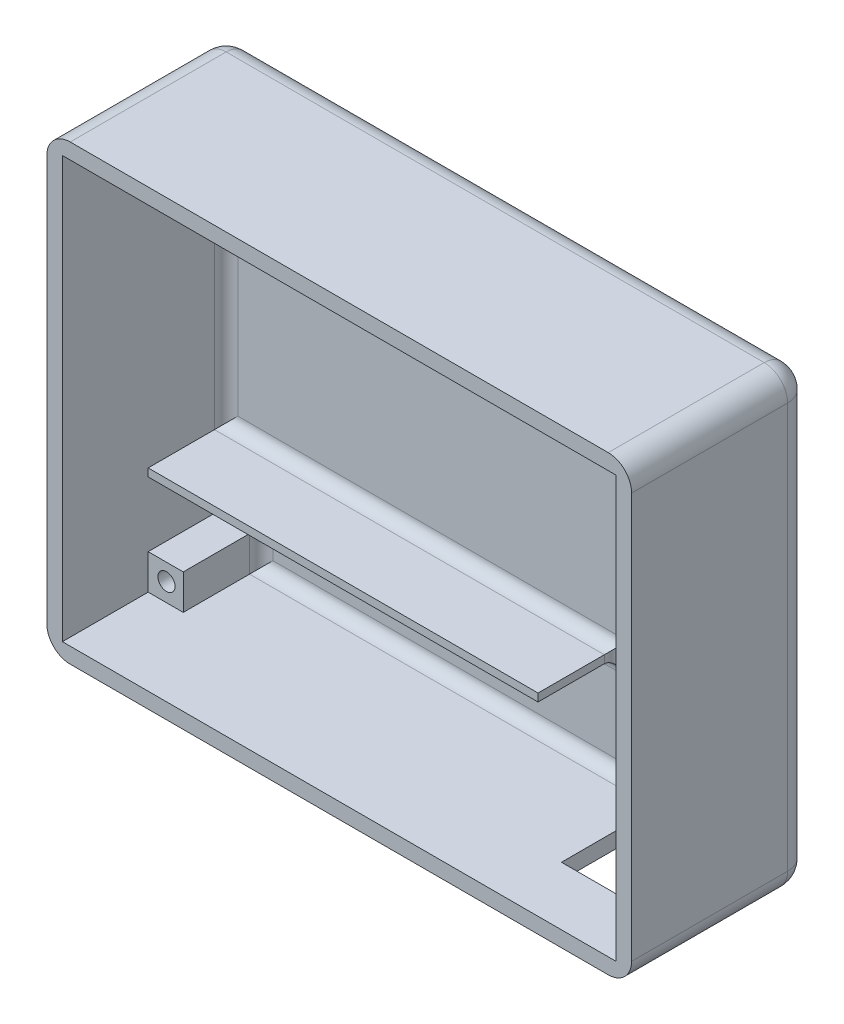
SolidWorks part; units mm, degrees
ref_plane "Front Plane" through (0, 0, 0) normal (0, 0, 1) x (1, 0, 0)
ref_plane "Top Plane" through (0, 0, 0) normal (0, 1, 0) x (1, 0, 0)
ref_plane "Right Plane" through (0, 0, 0) normal (1, 0, 0) x (0, 0, -1)
sketch "Sketch2" plane through (0, 0, 0) normal (0, 0, 1) x (1, 0, 0)
  line L1 (0, 0) -> (75, 0)
  line L2 (0, 0) -> (0, 58)
  line L3 (0, 58) -> (75, 58)
  line L4 (75, 0) -> (75, 58)
  dimension "D1" = 75
  dimension "D2" = 58
extrude "Body creation" add sketch "Sketch2" along normal blind 23
shell "Thikness of walls" thickness 2 removed face at (37.5, 29, 23)
ref_plane "Plane1" through (0, 29, 0) normal (0, -1, 0) x (-1, 0, 0)
sketch "Sketch6" plane through (0, 0, 2) normal (0, 0, 1) x (1, 0, 0)
  line L1 (2, 56) -> (6.5, 56)
  line L2 (2, 56) -> (2, 51.5)
  line L3 (2, 51.5) -> (6.5, 51.5)
  line L4 (6.5, 56) -> (6.5, 51.5)
  line L5 (73, 56) -> (68.5, 56)
  line L6 (73, 56) -> (73, 51.5)
  line L7 (73, 51.5) -> (68.5, 51.5)
  line L8 (68.5, 56) -> (68.5, 51.5)
  dimension "D1" = 4.5
extrude "Corner rect." add sketch "Sketch6" along normal blind 10
sketch "Sketch8" plane through (0, 0, 23) normal (0, 0, 1) x (1, 0, 0)
  line L0 (4.35, 53.65) -> (4.35, 51.5) construction
  line L1 (2, 51.5) -> (6.5, 51.5) construction
  line L2 (6.5, 53.65) -> (4.35, 53.65) construction
  line L3 (6.5, 51.5) -> (6.5, 56) construction
  line L4 (68.5, 53.65) -> (70.65, 53.65) construction
  line L7 (70.65, 53.65) -> (70.65, 51.5) construction
  line L9 (68.5, 56) -> (68.5, 51.5) construction
  line L10 (68.5, 51.5) -> (73, 51.5) construction
  circle A0 centre (4.35, 53.65) radius 1.1
  circle A1 centre (70.65, 53.65) radius 1.1
  dimension "D1" = 2.2
  dimension "D2" = 2.15
  dimension "D3" = 2.15
extrude "Screw hole" cut sketch "Sketch8" against normal up to surface (23 mm away) up to face at (37.5, 29, 0)
sketch "Sketch10" plane through (0, 0, 0) normal (0, 0, -1) x (-1, 0, 0)
  circle A0 centre (-70.65, 53.65) radius 1.85
  circle A1 centre (-4.35, 53.65) radius 1.85
  dimension "D1" = 3.7
extrude "Screw head" cut sketch "Sketch10" against normal blind 4
mirror "Mirror to other side" about plane through (0, 29, 0) normal (0, -1, 0) of "Screw head", "Corner rect.", "Screw hole"
sketch "Sketch5" plane through (0, 0, 0) normal (0, -1, 0) x (1, 0, 0)
  line L0 (0, 0) -> (75, 0) construction
  line L1 (67.5, 15.5) -> (58.5, 15.5)
  line L2 (67.5, 15.5) -> (67.5, 4.5)
  line L3 (67.5, 4.5) -> (58.5, 4.5)
  line L4 (58.5, 15.5) -> (58.5, 4.5)
  line L7 (63, 15.5) -> (63, 4.5) construction
  line L8 (75, 23) -> (75, 0) construction
  dimension "D1" = 11
  dimension "D2" = 9
  dimension "D3" = 15.5
  dimension "D4" = 12
extrude "Ports cut out" cut sketch "Sketch5" against normal up to surface (2 mm away) up to face at (37.5, 2, 12.25)
sketch "Sketch11" plane through (0, 0, 2) normal (0, 0, 1) x (1, 0, 0)
  line L0 (2, 51.5) -> (2, 6.5) construction
  line L1 (6.5, 51.5) -> (52, 51.5)
  line L3 (2, 15.8) -> (52, 15.8)
  line L5 (6.5, 52.5) -> (52, 52.5)
  line L6 (2, 14.8) -> (52, 14.8)
  line L7 (52, 15.8) -> (52, 14.8)
  line L8 (52, 52.5) -> (52, 51.5)
  line L9 (6.5, 52.5) -> (6.5, 51.5)
  line L10 (2, 15.8) -> (2, 14.8)
  line L11 (2, 56) -> (2, 2) construction
  line L12 (68.5, 56) -> (67.25, 56)
  line L13 (68.5, 56) -> (68.5, 33.5)
  line L14 (68.5, 33.5) -> (67.25, 33.5)
  line L15 (67.25, 56) -> (67.25, 33.5)
  line L16 (68.5, 56) -> (68.5, 51.5) construction
  line L18 (68.5, 56) -> (6.5, 56) construction
  dimension "D1" = 35.7
  dimension "D2" = 50
  dimension "D5" = 65.25
  dimension "D6" = 22.5
  dimension "D3" = 1
  dimension "D4" = 1
extrude "Battery Placement" add sketch "Sketch11" along normal blind 10
fillet "Fillet1" radius 1.5 20 edges at (2, 10.65, 2) (6.5, 54.25, 2) (29.25, 52.5, 2) (27, 14.8, 2) (2, 33.65, 2) (27, 51.5, 2) (52, 52, 2) (36.875, 56, 2) (70.75, 51.5, 2) (73, 29, 2) (70.75, 6.5, 2) (68.5, 4.25, 2) (37.5, 2, 2) (6.5, 4.25, 2) (4.25, 6.5, 2) (52, 15.3, 2) (27, 15.8, 2) (67.25, 44.75, 2) (67.875, 33.5, 2) (68.5, 42.5, 2)
fillet "Fillet2" radius 3 8 edges at (0, 58, 11.5) (75, 58, 11.5) (75, 0, 11.5) (0, 0, 11.5) (37.5, 58, 0) (75, 29, 0) (37.5, 0, 0) (0, 29, 0)
sketch "Sketch13" plane through (0, 0, 0) normal (0, 0, -1) x (-1, 0, 0)
  line L0 (-37.5, 49) -> (-37.5, 55) construction
  line L1 (-62.5, 49) -> (-12.5, 49)
  line L2 (-62.5, 49) -> (-62.5, 9)
  line L3 (-62.5, 9) -> (-12.5, 9)
  line L4 (-12.5, 49) -> (-12.5, 9)
  line L5 (-5.6149, 55) -> (-69.3851, 55) construction
  line L6 (-62.5, 29) -> (-72, 29) construction
  line L7 (-72, 52.3851) -> (-72, 5.6149) construction
  dimension "D1" = 50
  dimension "D2" = 40
extrude "Cut-Extrude1" cut sketch "Sketch13" against normal blind 1
